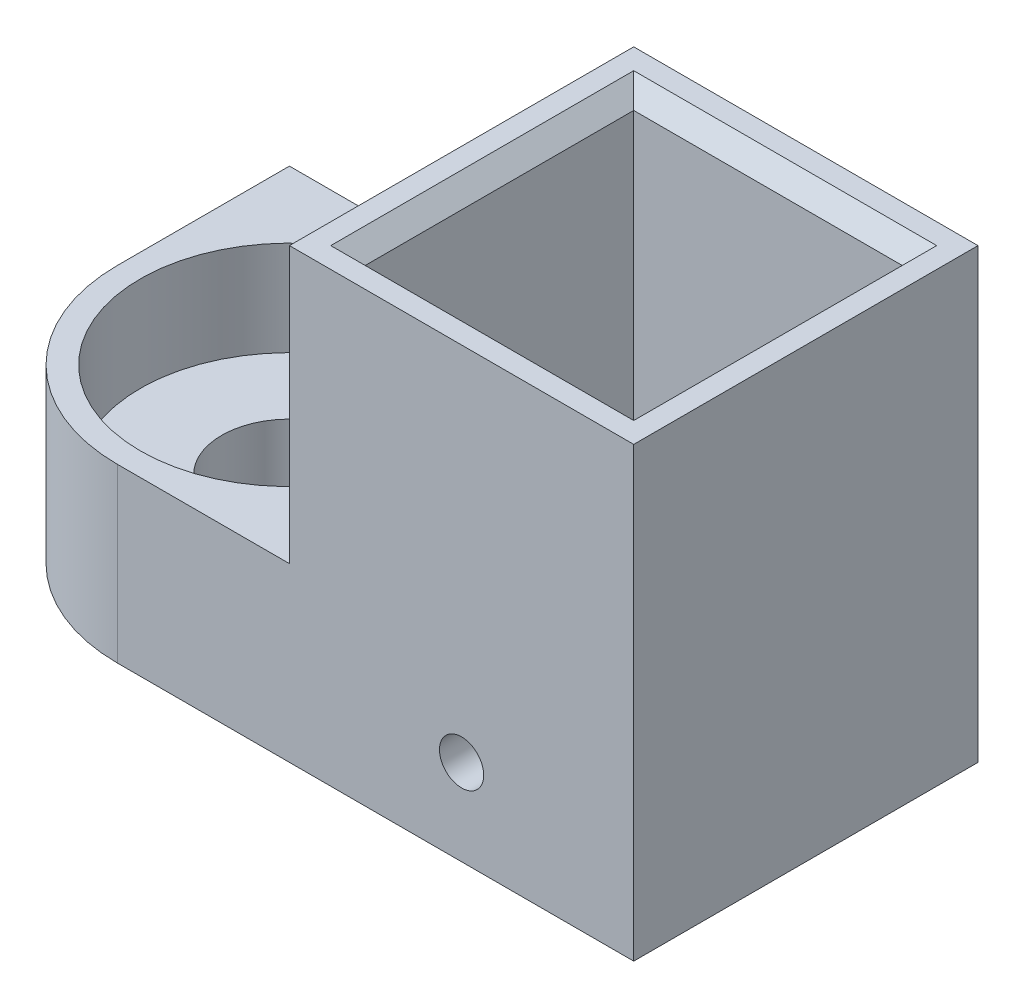
SolidWorks part; units mm, degrees
ref_plane "Front Plane" through (0, 0, 0) normal (0, 0, 1) x (1, 0, 0)
ref_plane "Top Plane" through (0, 0, 0) normal (0, 1, 0) x (1, 0, 0)
ref_plane "Right Plane" through (0, 0, 0) normal (1, 0, 0) x (0, 0, -1)
sketch "Sketch1" plane through (0, 0, 0) normal (0, 1, 0) x (1, 0, 0)
  line L1 (-12.7, 12.7) -> (12.7, 12.7)
  line L2 (-12.7, 12.7) -> (-12.7, -12.7)
  line L3 (-12.7, -12.7) -> (12.7, -12.7)
  line L4 (12.7, 12.7) -> (12.7, -12.7)
  line L5 (-12.7, 12.7) -> (12.7, -12.7) construction
  line L6 (-12.7, -12.7) -> (12.7, 12.7) construction
  line L7 (-9.906, -9.906) -> (9.906, -9.906)
  line L8 (-9.906, -9.906) -> (-9.906, 9.906)
  line L9 (-9.906, 9.906) -> (9.906, 9.906)
  line L10 (9.906, -9.906) -> (9.906, 9.906)
  line L11 (-9.906, -9.906) -> (9.906, 9.906) construction
  line L12 (-9.906, 9.906) -> (9.906, -9.906) construction
  point P0 (0, 0)
  point P6 (0, 0)
  dimension "D1" = 25.4
  dimension "D2" = 19.812
extrude "Boss-Extrude1" add sketch "Sketch1" along normal blind 33.02
sketch "Sketch9" plane through (0, 0, 0) normal (0, -1, 0) x (1, 0, 0)
  line L0 (-12.7, -12.7) -> (-12.7, 12.7) construction
  line L1 (-12.7, -12.7) -> (-12.7, 12.7)
  line L2 (-12.7, 12.7) -> (-38.1, 12.7)
  line L3 (-38.1, 12.7) -> (-38.1, -12.7)
  line L4 (-38.1, -12.7) -> (-12.7, -12.7)
  dimension "D1" = 25.4
extrude "Boss-Extrude5" add sketch "Sketch9" against normal blind 12.7
sketch "Sketch10" plane through (0, 12.7, 0) normal (0, 1, 0) x (1, 0, 0)
  line L0 (-38.1, 12.7) -> (-12.7, 12.7) construction
  line L1 (-38.1, -12.7) -> (-38.1, 12.7) construction
  circle A0 centre (-25.4, 0) radius 11
  point P4 (-25.4, 12.7)
  point P7 (-38.1, 0)
  dimension "D1" = 22
sketch "Sketch14" plane through (0, 0, 0) normal (0, -1, 0) x (1, 0, 0)
  line L0 (9.906, 9.906) -> (9.906, -9.906) construction
  line L1 (-9.906, 9.906) -> (9.906, 9.906) construction
  line L2 (-9.906, -9.906) -> (-9.906, 9.906) construction
  line L3 (9.906, -9.906) -> (-9.906, -9.906) construction
  line L4 (9.906, 9.906) -> (9.906, -9.906)
  line L5 (-9.906, 9.906) -> (9.906, 9.906)
  line L6 (-9.906, -9.906) -> (-9.906, 9.906)
  line L7 (9.906, -9.906) -> (-9.906, -9.906)
  line L8 (-8.001, 8.001) -> (8.001, 8.001)
  line L9 (8.001, 8.001) -> (8.001, -8.001)
  line L10 (8.001, -8.001) -> (-8.001, -8.001)
  line L11 (-8.001, -8.001) -> (-8.001, 8.001)
  dimension "D1" = 1.905
extrude "Boss-Extrude6" add sketch "Sketch14" against normal blind 2.54
extrude "Cut-Extrude1" cut sketch "Sketch10" against normal blind 7
sketch "Sketch15" plane through (0, 5.7, 0) normal (0, 1, 0) x (1, 0, 0)
  circle A0 centre (-25.4, 0) radius 5
  circle A1 centre (-25.4, 0) radius 11 construction
  dimension "D1" = 10
extrude "Cut-Extrude2" cut sketch "Sketch15" against normal up to next
sketch "Sketch17" plane through (0, 0, 0) normal (0, -1, 0) x (1, 0, 0)
  line L0 (-12.7, -12.7) -> (-12.7, 12.7) construction
  line L1 (-38.1, -12.7) -> (-12.7, -12.7)
  line L2 (-38.1, -12.7) -> (-38.1, -38.1)
  line L3 (-38.1, -38.1) -> (-12.7, -38.1)
  line L4 (-12.7, -12.7) -> (-12.7, -38.1)
  dimension "D1" = 25.4
extrude "Boss-Extrude7" add sketch "Sketch17" against normal blind 6.35
sketch "Sketch18" plane through (0, 0, 0) normal (0, -1, 0) x (1, 0, 0)
  line L0 (-38.1, -38.1) -> (-12.7, -38.1) construction
  line L1 (-12.7, -38.1) -> (-12.7, -12.7) construction
  circle A0 centre (-25.4, -25.4) radius 6.5
  point P4 (-25.4, -38.1)
  point P7 (-12.7, -25.4)
  dimension "D1" = 13
extrude "Cut-Extrude4" cut sketch "Sketch18" against normal up to next
hole_wizard "M3 Clearance Hole1" positions "Sketch20" profile "Sketch22" hole size "M3" standard "ANSI Metric"
sketch "Sketch20" plane through (0, 0, 0) normal (0, -1, 0) x (-1, 0, 0)
  line L0 (12.7, 38.1) -> (12.7, 12.7) construction
  circle A0 centre (25.4, 25.4) radius 6.5 construction
  point P0 (16.4, 25.4)
  point P5 (12.7, 25.4)
  dimension "D1" = 9
sketch "Sketch22" plane through (-16.4, 0, -25.4) normal (1, 0, 0) x (0, 0, -1)
  line L0 (0, 0) -> (0, 13.7215)
  line L1 (0, 13.7215) -> (1.7, 12.7)
  line L2 (1.7, 12.7) -> (1.7, 0)
  line L5 (1.7, 0) -> (0, 0)
  line L10 (0, 13.7215) -> (-1.7, 12.7) construction
  line L11 (0, -6.35) -> (0, 107.95) construction
  dimension "Hole Dia." = 3.4
  dimension "Hole Depth" = 12.7
  dimension "Drill Angle" = 118
pattern_circular "CirPattern1" count 4 over 360 about axis through (-25.4, 0, -25.4) along (0, -1, 0) of "M3 Clearance Hole1"
sketch "Sketch23" plane through (0, 6.35, 0) normal (0, 1, 0) x (1, 0, 0)
  circle A0 centre (-25.4, 34.4) radius 3.25
  circle A1 centre (-25.4, 34.4) radius 1.7 construction
  point P2 (0, 0)
  dimension "D1" = 6.5
extrude "Cut-Extrude5" cut sketch "Sketch23" against normal blind 2.75
pattern_circular "CirPattern2" count 4 over 360 about axis through (-25.4, 33.021, -25.4) along (0, -1, 0) of "Cut-Extrude5" reverse direction yes
fillet "Fillet3" radius 12.7 3 edges at (-38.1, 3.175, -38.1) (-12.7, 3.175, -38.1) (-38.1, 6.35, 12.7)
fillet "Fillet4" radius 1.27 4 edges at (8.001, 1.27, -8.001) (8.001, 1.27, 8.001) (-8.001, 1.27, 8.001) (-8.001, 1.27, -8.001)
fillet "Fillet5" radius 1.27 16 edges at (-7.629, 2.54, -7.629) (-8.001, 2.54, 0) (-7.629, 2.54, 7.629) (0, 2.54, 8.001) (7.629, 2.54, 7.629) (8.001, 2.54, 0) (7.629, 2.54, -7.629) (-7.629, 0, -7.629) (-8.001, 0, 0) (-7.629, 0, 7.629) (0, 0, 8.001) (7.629, 0, 7.629) (8.001, 0, 0) (7.629, 0, -7.629) (0, 2.54, -8.001) (0, 0, -8.001)
hole_wizard "#4 Clearance Hole1" positions "Sketch24" profile "Sketch25" hole size "#4" standard "ANSI Inch" end condition through all
sketch "Sketch24" plane through (0, 0, 12.7) normal (0, 0, 1) x (1, 0, 0)
  line L0 (-25.4, 0) -> (12.7, 0) construction
  line L1 (-9.906, 33.02) -> (9.906, 33.02) construction
  point P0 (0, 6.35)
  point P5 (0, 0)
  point P7 (0, 0)
  point P10 (0, 33.02)
  dimension "D1" = 6.35
sketch "Sketch25" plane through (0, 6.35, 12.7) normal (1, 0, 0) x (0, -1, 0)
  line L0 (0, 0) -> (0, 50.8)
  line L1 (0, 50.8) -> (1.6319, 50.8)
  line L2 (1.6319, 50.8) -> (1.6319, 0)
  line L5 (1.6319, 0) -> (0, 0)
  line L11 (0, -6.35) -> (0, 107.95) construction
  dimension "Thru Hole Dia." = 3.2639
  dimension "Thru Hole Depth" = 50.8
chamfer "Chamfer1" distance 1.27 angle 45 4 edges at (-9.906, 33.02, 0) (0, 33.02, 9.906) (0, 33.02, -9.906) (9.906, 33.02, 0)
equation "\"TOL\"= .01"
equation "\"D2@Sketch1\"=.76+\"TOL\"*2"
